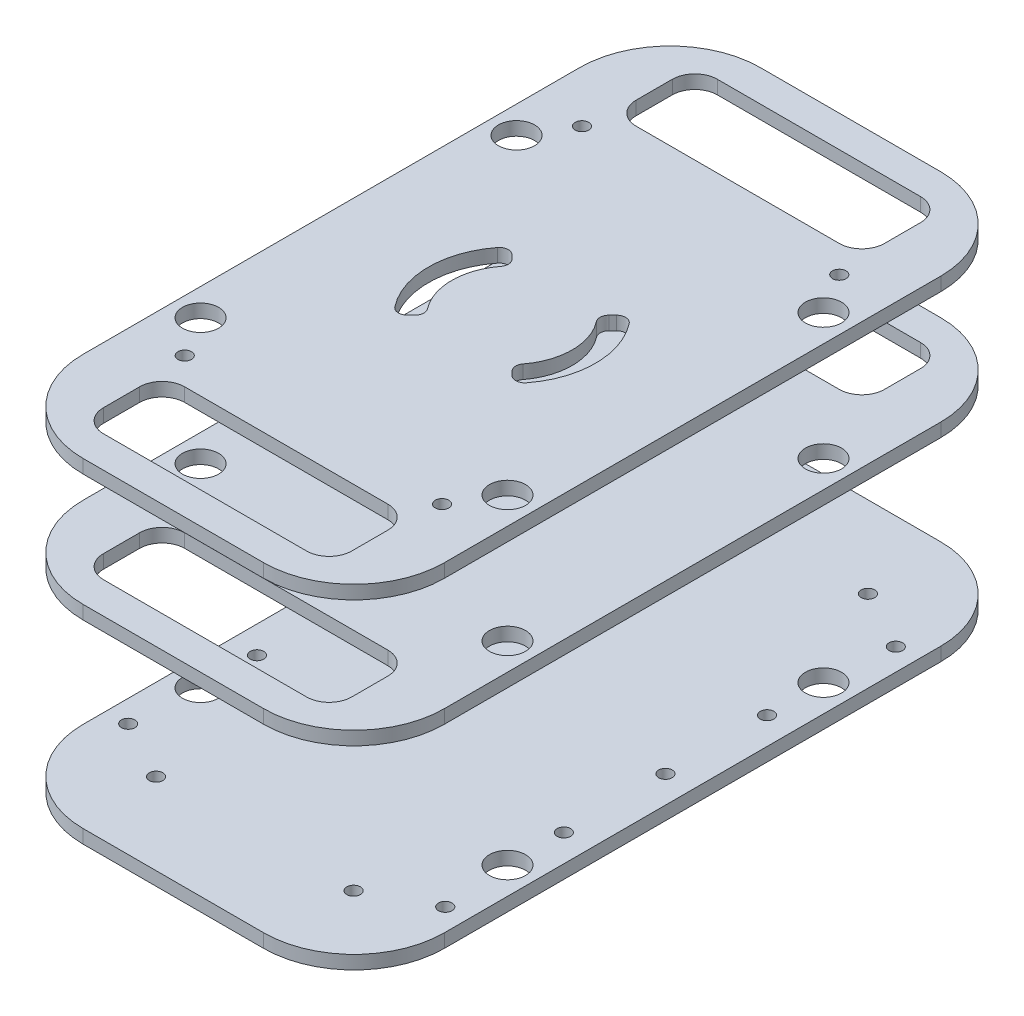
SolidWorks part; units mm, degrees
ref_plane "Front Plane" through (0, 0, 0) normal (0, 0, 1) x (1, 0, 0)
ref_plane "Top Plane" through (0, 0, 0) normal (0, 1, 0) x (1, 0, 0)
ref_plane "Right Plane" through (0, 0, 0) normal (1, 0, 0) x (0, 0, -1)
sketch "Sketch1" plane through (0, 0, 0) normal (0, 1, 0) x (1, 0, 0)
  line L0 (40, -75) -> (82.3529, -154.4118) construction
  line L1 (-20, -75) -> (20, -75)
  line L2 (-40, -55) -> (-40, 55)
  line L3 (-20, 75) -> (20, 75)
  line L4 (40, -55) -> (40, 55)
  line L5 (-40, -75) -> (40, 75) construction
  line L6 (-40, 75) -> (40, -75) construction
  line L7 (-40, -75) -> (-82.3529, -154.4118) construction
  line L8 (40, 75) -> (82.3529, 154.4118) construction
  line L9 (-40, 75) -> (-82.3529, 154.4118) construction
  line L10 (9.7604, -75) -> (28.5, -53.4375) construction
  line L11 (-28.5, -53.4375) -> (28.5, -53.4375) construction
  line L12 (-28.5, -53.4375) -> (-28.5, 53.4375) construction
  line L13 (-28.5, 53.4375) -> (28.5, 53.4375) construction
  line L14 (28.5, -53.4375) -> (28.5, 53.4375) construction
  line L15 (-28.5, -53.4375) -> (28.5, 53.4375) construction
  line L16 (-28.5, 53.4375) -> (28.5, -53.4375) construction
  line L17 (28.5, -53.4375) -> (40, -40.2052) construction
  line L18 (0, 0) -> (0, -154.4118) construction
  line L19 (0, 0) -> (104.2564, 0) construction
  line L20 (21.8824, -56.9669) -> (35.1176, -49.9081) construction
  line L21 (0, 0) -> (33.2783, 17.7484) construction
  circle A0 centre (0, 0) radius 175 construction
  arc A1 (-40, 55) -> (-20, 75) centre (-20, 55) cw
  arc A2 (20, 75) -> (40, 55) centre (20, 55) cw
  arc A3 (20, -75) -> (40, -55) centre (20, -55) ccw
  arc A4 (-20, -75) -> (-40, -55) centre (-20, -55) cw
  circle A6 centre (-34, 35) radius 4
  circle A7 centre (34, 35) radius 4
  circle A8 centre (34, -35) radius 4
  circle A9 centre (-34, -35) radius 4
  circle A10 centre (21.8824, -56.9669) radius 1.5
  circle A11 centre (35.1176, -49.9081) radius 1.5
  circle A12 centre (-35.1176, 49.9081) radius 1.5
  circle A13 centre (-21.8824, 56.9669) radius 1.5
  circle A14 centre (35.1176, 49.9081) radius 1.5
  circle A15 centre (21.8824, 56.9669) radius 1.5
  circle A16 centre (-21.8824, -56.9669) radius 1.5
  circle A17 centre (-35.1176, -49.9081) radius 1.5
  dimension "D1" = 350
  dimension "D4" = 20
  dimension "D5" = 57
  dimension "D6" = 8
  dimension "D10" = 3
  dimension "D11" = 3
  dimension "D2" = 150
  dimension "D3" = 80
  dimension "D7" = 6
  dimension "D8" = 40
  dimension "D9" = 15
extrude "Boss-Extrude1" add sketch "Sketch1" along normal blind 3
extrude "Boss-Extrude2" add sketch "Sketch1<2>" along normal blind 3 from offset 43 separate body contours A4 L1 A3 L4 A2 L3 A1 L2 A11 A10 A7 A6 A8 A9 | A11 | A16 | A17 | A10 | A13 | A12 | A15 | A14 region at (0, 0, 0) region at (21.8824, 0, 56.9669) region at (35.1176, 0, 49.9081) region at (-35.1176, 0, -49.9081) region at (-21.8824, 0, -56.9669) region at (35.1176, 0, -49.9081) region at (21.8824, 0, -56.9669) region at (-21.8824, 0, 56.9669) region at (-35.1176, 0, 49.9081)
sketch "Sketch1<2>" plane through (0, 0, 0) normal (0, 1, 0) x (1, 0, 0) same geometry as "Sketch1"
extrude "Boss-Extrude3" add sketch "Sketch1<3>" along normal blind 3 from offset 71 separate body contours A4 L1 A3 L4 A2 L3 A1 L2 A16 A15 A14 A12 A11 A10 A7 A6 A8 A9 A13 A17 | A13 | A12 | A15 | A14 | A11 | A10 | A17 | A16 region at (0, 0, 0) region at (21.8824, 0, 56.9669) region at (35.1176, 0, 49.9081) region at (-35.1176, 0, -49.9081) region at (-21.8824, 0, -56.9669) region at (35.1176, 0, -49.9081) region at (21.8824, 0, -56.9669) region at (-21.8824, 0, 56.9669) region at (-35.1176, 0, 49.9081)
sketch "Sketch1<3>" plane through (0, 0, 0) normal (0, 1, 0) x (1, 0, 0) same geometry as "Sketch1"
sketch "Sketch3" plane through (0, 74, 0) normal (0, 1, 0) x (1, 0, 0)
  line L0 (0, 0) -> (0, -20.0347) construction
  line L1 (-30, 47) -> (30, 47)
  line L2 (-30, 47) -> (-30, -47)
  line L3 (-30, -47) -> (30, -47)
  line L4 (30, 47) -> (30, -47)
  line L5 (-30, 47) -> (30, -47) construction
  line L6 (-30, -47) -> (30, 47) construction
  circle A0 centre (-28.5, 44) radius 1.5
  circle A1 centre (-28.5, -44) radius 1.5
  circle A2 centre (28.5, -44) radius 1.5
  circle A3 centre (28.5, 44) radius 1.5
  point P0 (0, 0)
  point P6 (-28.5, 44)
  point P7 (-28.5, -44)
  point P8 (28.5, -44)
  point P9 (28.5, 44)
  dimension "D7" = 3
  dimension "D8" = 3
  dimension "D1" = 94
  dimension "D2" = 60
  dimension "D3" = 88
  dimension "D4" = 3
  dimension "D5" = 57
  dimension "D6" = 1.5
extrude "Cut-Extrude1" cut sketch "Sketch3" against normal blind 10 contours A3 | A0 | A1 | A2 region at (-28.5, 74, -44) region at (-28.5, 74, 44) region at (28.5, 74, 44) region at (28.5, 74, -44)
sketch "Sketch4" plane through (0, 74, 0) normal (0, 1, 0) x (1, 0, 0)
  line L0 (0, 0) -> (27.5, 0) construction
  line L1 (-22.5, 68.0049) -> (22.5, 68.0049)
  line L2 (-27.5, 63.0049) -> (-27.5, 55.0049)
  line L3 (-22.5, 50.0049) -> (22.5, 50.0049)
  line L4 (27.5, 63.0049) -> (27.5, 55.0049)
  line L5 (-27.5, 68.0049) -> (27.5, 50.0049) construction
  line L6 (-27.5, 50.0049) -> (27.5, 68.0049) construction
  line L7 (-27.5, -63.0049) -> (-27.5, -55.0049)
  line L8 (-22.5, -68.0049) -> (22.5, -68.0049)
  line L9 (27.5, -63.0049) -> (27.5, -55.0049)
  line L10 (-22.5, -50.0049) -> (22.5, -50.0049)
  line L11 (11.5769, 11.5769) -> (10.7587, 10.7587)
  line L12 (-14.5, 22.5) -> (14.5, 22.5)
  line L13 (-22.5, 14.5) -> (-22.5, -14.5)
  line L14 (-14.5, -22.5) -> (14.5, -22.5)
  line L15 (22.5, 14.5) -> (22.5, -14.5)
  line L16 (-22.5, 22.5) -> (22.5, -22.5) construction
  line L17 (-22.5, -22.5) -> (22.5, 22.5) construction
  line L18 (11.5769, -11.5769) -> (10.7587, -10.7587)
  line L19 (-10.7587, 10.7587) -> (-11.5769, 11.5769)
  line L20 (-10.7587, -10.7587) -> (-11.5769, -11.5769)
  line L21 (20.5, 14.5) -> (20.5, -14.5)
  line L22 (-14.5, -20.5) -> (14.5, -20.5)
  line L23 (-20.5, 14.5) -> (-20.5, -14.5)
  line L24 (-14.5, 20.5) -> (14.5, 20.5)
  arc A0 (22.5, -68.0049) -> (27.5, -63.0049) centre (22.5, -63.0049) ccw
  arc A1 (-27.5, -63.0049) -> (-22.5, -68.0049) centre (-22.5, -63.0049) ccw
  arc A2 (-27.5, 55.0049) -> (-22.5, 50.0049) centre (-22.5, 55.0049) ccw
  arc A3 (22.5, 50.0049) -> (27.5, 55.0049) centre (22.5, 55.0049) ccw
  arc A4 (27.5, -55.0049) -> (22.5, -50.0049) centre (22.5, -55.0049) ccw
  arc A5 (-27.5, -55.0049) -> (-22.5, -50.0049) centre (-22.5, -55.0049) cw
  arc A6 (-22.5, 68.0049) -> (-27.5, 63.0049) centre (-22.5, 63.0049) ccw
  arc A7 (22.5, 68.0049) -> (27.5, 63.0049) centre (22.5, 63.0049) cw
  arc A8 (14.5664, -11.395) -> (14.5664, 11.395) centre (0, 0) ccw
  arc A9 (-10.5864, 8.1266) -> (-10.5864, -8.1266) centre (0, 0) ccw
  arc A10 (10.5864, -8.1266) -> (10.5864, 8.1266) centre (0, 0) ccw
  arc A11 (-14.5664, 11.395) -> (-14.5664, -11.395) centre (0, 0) ccw
  arc A12 (-11.5769, -11.5769) -> (-14.5664, -11.395) centre (-12.9911, -10.1627) cw
  arc A13 (-10.7587, -10.7587) -> (-10.5864, -8.1266) centre (-12.1729, -9.3444) ccw
  arc A14 (-11.5769, 11.5769) -> (-14.5664, 11.395) centre (-12.9911, 10.1627) ccw
  arc A15 (-10.7587, 10.7587) -> (-10.5864, 8.1266) centre (-12.1729, 9.3444) cw
  arc A16 (11.5769, -11.5769) -> (14.5664, -11.395) centre (12.9911, -10.1627) ccw
  arc A17 (10.7587, -10.7587) -> (10.5864, -8.1266) centre (12.1729, -9.3444) cw
  arc A18 (11.5769, 11.5769) -> (14.5664, 11.395) centre (12.9911, 10.1627) cw
  arc A19 (10.7587, 10.7587) -> (10.5864, 8.1266) centre (12.1729, 9.3444) ccw
  arc A20 (-14.5, 22.5) -> (-22.5, 14.5) centre (-14.5, 14.5) ccw
  arc A21 (-22.5, -14.5) -> (-14.5, -22.5) centre (-14.5, -14.5) ccw
  arc A22 (14.5, -22.5) -> (22.5, -14.5) centre (14.5, -14.5) ccw
  arc A23 (14.5, 22.5) -> (22.5, 14.5) centre (14.5, 14.5) cw
  arc A24 (14.5, -20.5) -> (20.5, -14.5) centre (14.5, -14.5) ccw
  arc A25 (-20.5, -14.5) -> (-14.5, -20.5) centre (-14.5, -14.5) ccw
  arc A26 (-14.5, 20.5) -> (-20.5, 14.5) centre (-14.5, 14.5) ccw
  arc A27 (14.5, 20.5) -> (20.5, 14.5) centre (14.5, 14.5) cw
  point P0 (0, 59.0049)
  point P1 (0, 59.0049)
  point P6 (0, 0)
  point P16 (27.5, -68.0049)
  point P19 (-27.5, -68.0049)
  point P28 (27.5, -50.0049)
  point P31 (-27.5, -50.0049)
  point P52 (-13.0772, -13.0772)
  point P55 (-9.437, -9.437)
  point P58 (-13.0772, 13.0772)
  point P61 (-9.437, 9.437)
  point P64 (13.0772, -13.0772)
  point P67 (9.437, -9.437)
  dimension "D3" = 5
  dimension "D6" = 2
  dimension "D7" = 8
  dimension "D1" = 18
  dimension "D2" = 55
  dimension "D4" = 45
  dimension "D5" = 45
  dimension "D8" = 2
extrude "Cut-Extrude2" cut sketch "Sketch4" against normal up to surface (31 mm away) contours A7 L1 A6 L2 A2 L3 A3 L4 | A5 L7 A1 L8 A0 L9 A4 L10 | L11 A19 A10 A17 L18 A16 A8 A18 | A15 L19 A14 A11 A12 L20 A13 A9 region at (0, 74, -59.0049) region at (0, 74, 59.0049) region at (14.5298, 74, 0) region at (-14.5298, 74, 0) up to face at (34, 43, -31)
sketch "Sketch5" plane through (0, 46, 0) normal (0, 1, 0) x (1, 0, 0)
  line L0 (-27.5, -63.0049) -> (-27.5, -55.0049) construction
  line L1 (27.5, -63.0049) -> (27.5, -55.0049) construction
  line L2 (-22.5, -68.0049) -> (22.5, -68.0049) construction
  line L3 (-22.5, -50.0049) -> (22.5, -50.0049) construction
  line L4 (-20, -75) -> (20, -75)
  line L5 (40, -55) -> (40, 55)
  line L6 (20, 75) -> (-20, 75)
  line L7 (-40, 55) -> (-40, -55)
  line L8 (-20, -75) -> (20, -75)
  line L9 (40, -55) -> (40, 55)
  line L10 (20, 75) -> (-20, 75)
  line L11 (-40, 55) -> (-40, -55)
  line L12 (-20, -75) -> (20, -75)
  line L13 (40, -55) -> (40, 55)
  line L14 (20, 75) -> (-20, 75)
  line L15 (-40, 55) -> (-40, -55)
  line L16 (-20, -75) -> (20, -75)
  line L17 (40, -55) -> (40, 55)
  line L18 (20, 75) -> (-20, 75)
  line L19 (-40, 55) -> (-40, -55)
  line L20 (-27.5, -63.0049) -> (-27.5, -55.0049)
  line L21 (27.5, -63.0049) -> (27.5, -55.0049)
  line L22 (-22.5, -68.0049) -> (22.5, -68.0049)
  line L23 (-22.5, -50.0049) -> (22.5, -50.0049)
  line L24 (0, 0) -> (-73.8796, 0) construction
  line L25 (27.5, 63.0049) -> (27.5, 55.0049)
  line L26 (-22.5, 68.0049) -> (22.5, 68.0049)
  line L27 (-27.5, 63.0049) -> (-27.5, 55.0049)
  line L28 (-22.5, 50.0049) -> (22.5, 50.0049)
  arc A0 (-22.5, -50.0049) -> (-27.5, -55.0049) centre (-22.5, -55.0049) ccw construction
  arc A1 (-27.5, -63.0049) -> (-22.5, -68.0049) centre (-22.5, -63.0049) ccw construction
  arc A2 (27.5, -55.0049) -> (22.5, -50.0049) centre (22.5, -55.0049) ccw construction
  arc A3 (22.5, -68.0049) -> (27.5, -63.0049) centre (22.5, -63.0049) ccw construction
  arc A4 (-40, -55) -> (-20, -75) centre (-20, -55) ccw
  arc A5 (20, -75) -> (40, -55) centre (20, -55) ccw
  arc A6 (40, 55) -> (20, 75) centre (20, 55) ccw
  arc A7 (-20, 75) -> (-40, 55) centre (-20, 55) ccw
  arc A8 (-40, -55) -> (-20, -75) centre (-20, -55) ccw
  arc A9 (20, -75) -> (40, -55) centre (20, -55) ccw
  arc A10 (40, 55) -> (20, 75) centre (20, 55) ccw
  arc A11 (-20, 75) -> (-40, 55) centre (-20, 55) ccw
  arc A12 (-40, -55) -> (-20, -75) centre (-20, -55) ccw
  arc A13 (20, -75) -> (40, -55) centre (20, -55) ccw
  arc A14 (40, 55) -> (20, 75) centre (20, 55) ccw
  arc A15 (-20, 75) -> (-40, 55) centre (-20, 55) ccw
  arc A16 (-40, -55) -> (-20, -75) centre (-20, -55) ccw
  arc A17 (20, -75) -> (40, -55) centre (20, -55) ccw
  arc A18 (40, 55) -> (20, 75) centre (20, 55) ccw
  arc A19 (-20, 75) -> (-40, 55) centre (-20, 55) ccw
  arc A20 (-22.5, -50.0049) -> (-27.5, -55.0049) centre (-22.5, -55.0049) ccw
  arc A21 (-27.5, -63.0049) -> (-22.5, -68.0049) centre (-22.5, -63.0049) ccw
  arc A22 (27.5, -55.0049) -> (22.5, -50.0049) centre (22.5, -55.0049) ccw
  arc A23 (22.5, -68.0049) -> (27.5, -63.0049) centre (22.5, -63.0049) ccw
  arc A24 (27.5, 55.0049) -> (22.5, 50.0049) centre (22.5, 55.0049) cw
  arc A25 (22.5, 68.0049) -> (27.5, 63.0049) centre (22.5, 63.0049) cw
  arc A26 (-27.5, 63.0049) -> (-22.5, 68.0049) centre (-22.5, 63.0049) cw
  arc A27 (-22.5, 50.0049) -> (-27.5, 55.0049) centre (-22.5, 55.0049) cw
  dimension "D1" = 0
  dimension "D2" = 0
extrude "Cut-Extrude3" cut sketch "Sketch5" against normal blind 10 contours A27 L28 A24 L25 A25 L26 A26 L27 | L22 A23 L21 A22 L23 A20 L20 A21 region at (0, 46, 59.0049) region at (0, 46, -59.0049)
sketch "Sketch6" plane through (0, 3, 0) normal (0, 1, 0) x (1, 0, 0)
  line L0 (0, 0) -> (-74.7653, 0) construction
  line L1 (0, 0) -> (0, -46.7868) construction
  circle A0 centre (-34, 22.5) radius 1.5
  circle A1 centre (-34, -22.5) radius 1.5
  circle A2 centre (-34, 0) radius 1.5
  circle A3 centre (34, -22.5) radius 1.5
  circle A4 centre (34, 0) radius 1.5
  circle A5 centre (34, 22.5) radius 1.5
  point P3 (-34, -35)
  point P4 (-34, -22.5)
  point P6 (-34, 22.5)
  dimension "D3" = 3
  dimension "D4" = 3
  dimension "D5" = 3
  dimension "D1" = 22.5
  dimension "D2" = 45
extrude "Cut-Extrude5" cut sketch "Sketch6" against normal blind 31
